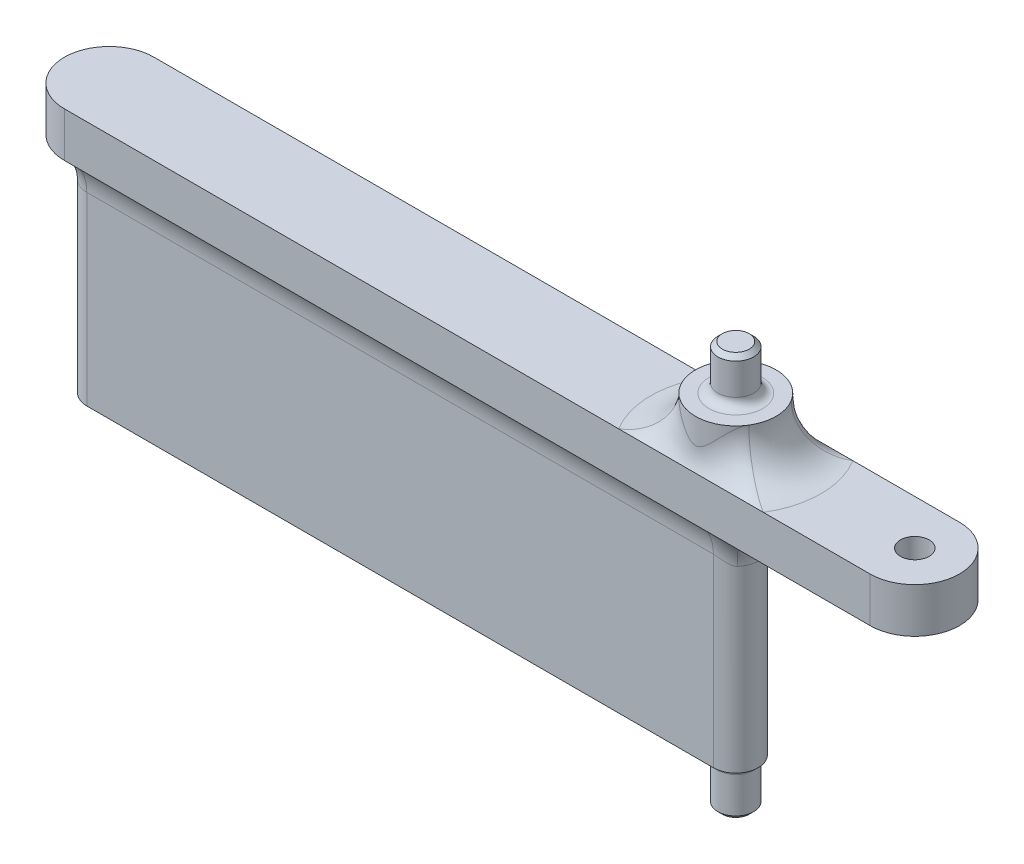
SolidWorks part; units mm, degrees
material "PET"
ref_plane "Front Plane" through (0, 0, 0) normal (0, 0, 1) x (1, 0, 0)
ref_plane "Top Plane" through (0, 0, 0) normal (0, 1, 0) x (1, 0, 0)
ref_plane "Right Plane" through (0, 0, 0) normal (1, 0, 0) x (0, 0, -1)
sketch "Sketch1" plane through (0, 0, 0) normal (0, 1, 0) x (1, 0, 0)
  line L0 (0, 0) -> (-140, 0) construction
  line L1 (0, -5) -> (-140, -5)
  line L2 (0, 5) -> (-140, 5)
  arc A0 (0, -5) -> (0, 5) centre (0, 0) ccw
  arc A1 (-140, 5) -> (-140, -5) centre (-140, 0) ccw
  point P3 (-70, 0)
  dimension "D1" = 140
  dimension "D2" = 10
extrude "Boss-Extrude1" add sketch "Sketch1" against normal blind 50
sketch "Sketch2" plane through (0, 0, 0) normal (0, 1, 0) x (1, 0, 0)
  line L0 (0, 0) -> (-140, 0) construction
  line L5 (-70, -10) -> (-140, -10)
  line L6 (-70, 10) -> (-140, 10)
  line L7 (0, 0) -> (40, 0) construction
  line L8 (-70, 10) -> (40, 10)
  line L9 (-70, -10) -> (40, -10)
  arc A5 (-140, 10) -> (-140, -10) centre (-140, 0) ccw
  arc A7 (40, -10) -> (40, 10) centre (40, 0) ccw
  circle A8 centre (40, 0) radius 3.2
  dimension "D5" = 6.4
  dimension "D7" = 10
  dimension "D1" = 140
  dimension "D2" = 20
  dimension "D3" = 20
  dimension "D4" = 40
  dimension "D6" = 70
extrude "Boss-Extrude2" add sketch "Sketch2" along normal blind 10
fillet "Fillet1" radius 10 3 edges at (5, 0, 0) (-70, 0, -5) (-70, 0, 5)
sketch "Sketch3" plane through (0, 10, 0) normal (0, 1, 0) x (1, 0, 0)
  circle A0 centre (0, 0) radius 9
  dimension "D1" = 18
extrude "Boss-Extrude3" add sketch "Sketch3" along normal blind 10
fillet "Fillet2" radius 10 1 edges at (0, 10, 9)
sketch "Sketch7" plane through (0, -50, 0) normal (0, -1, 0) x (1, 0, 0)
  circle A0 centre (0, 0) radius 4
  dimension "D1" = 8
extrude "Boss-Extrude4" add sketch "Sketch7" along normal blind 10
chamfer "Chamfer1" distance 1 angle 45 1 edges at (0, -60, -4)
sketch "Sketch8" plane through (0, 20, 0) normal (0, 1, 0) x (1, 0, 0)
  circle A1 centre (0, 0) radius 4
  dimension "D1" = 8
extrude "Boss-Extrude5" add sketch "Sketch8" along normal blind 10
chamfer "Chamfer2" distance 1 angle 45 1 edges at (0, 30, 4)
fillet "Fillet4" radius 1 1 edges at (0, -50, 4)
fillet "Fillet5" radius 2 1 edges at (0, 20, 4)
